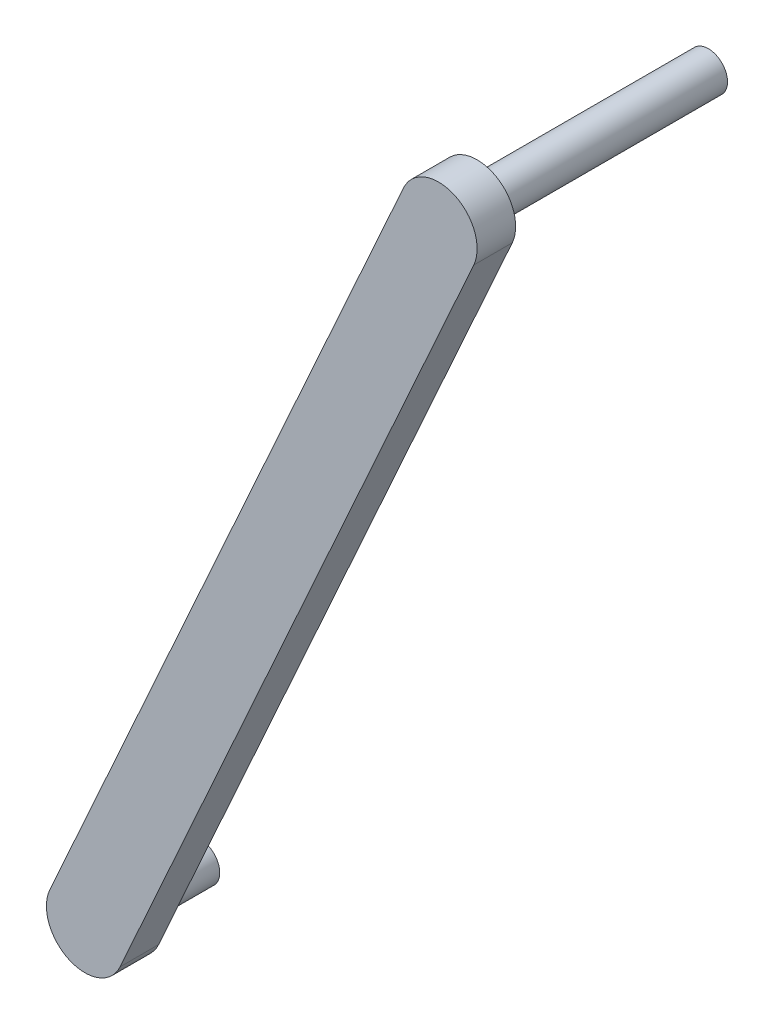
SolidWorks part; units mm, degrees
ref_plane "Front Plane" through (0, 0, 0) normal (0, 0, 1) x (1, 0, 0)
ref_plane "Top Plane" through (0, 0, 0) normal (0, 1, 0) x (1, 0, 0)
ref_plane "Right Plane" through (0, 0, 0) normal (1, 0, 0) x (0, 0, -1)
sketch "Sketch1" plane through (0, 0, 14.8753) normal (0, 0, 1) x (1, 0, 0)
  line L0 (0.9247, -18.2644) -> (-17.438, -58.9997) construction
  line L1 (2.748, -19.0864) -> (-15.6147, -59.8216)
  line L2 (-0.8986, -17.4425) -> (-19.2613, -58.1778)
  arc A0 (2.748, -19.0864) -> (-0.8986, -17.4425) centre (0.9247, -18.2644) ccw
  arc A1 (-19.2613, -58.1778) -> (-15.6147, -59.8216) centre (-17.438, -58.9997) ccw
  circle A2 centre (0.9247, -18.2644) radius 1
  circle A3 centre (-17.438, -58.9997) radius 1
  point P4 (-8.2566, -38.6321)
  dimension "D1" = 2
  dimension "D2" = 2
  dimension "D3" = 2
extrude "Boss-Extrude1" add sketch "Sketch1" along normal blind 2 contours L2 A1 L1 A0
extrude "Boss-Extrude2" add sketch "Sketch1<3>" against normal blind 4 contours A3
sketch "Sketch1<3>" plane through (0, 0, 14.8753) normal (0, 0, 1) x (1, 0, 0) same geometry as "Sketch1"
extrude "Boss-Extrude3" add sketch "Sketch1<4>" against normal blind 12 contours A2 region at (0.9247, -18.2644, 14.8753)
sketch "Sketch1<4>" plane through (0, 0, 14.8753) normal (0, 0, 1) x (1, 0, 0) same geometry as "Sketch1"
